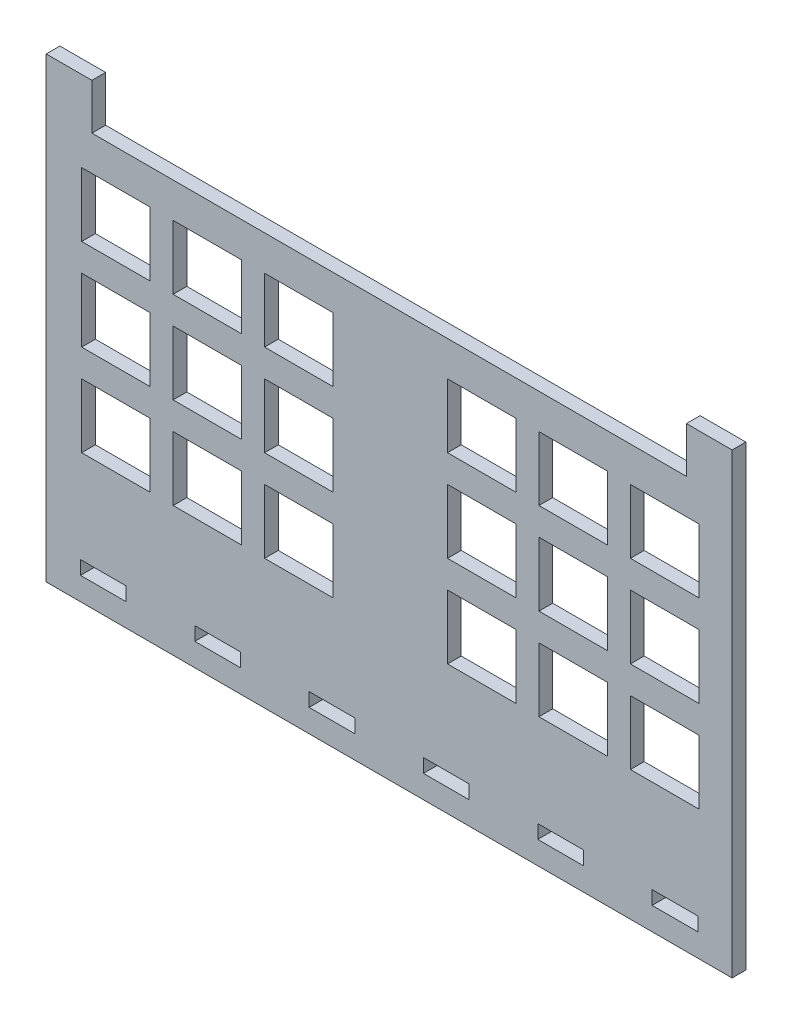
SolidWorks part; units mm, degrees
ref_plane "Plan de face" through (0, 0, 0) normal (0, 0, 1) x (1, 0, 0)
ref_plane "Plan de dessus" through (0, 0, 0) normal (0, 1, 0) x (1, 0, 0)
ref_plane "Plan de droite" through (0, 0, 0) normal (1, 0, 0) x (0, 0, -1)
sketch "Esquisse1" plane through (0, 0, 0) normal (0, 0, 1) x (1, 0, 0)
  line L1 (0, 0) -> (150, 0)
  line L2 (0, 0) -> (0, 100)
  line L3 (0, 100) -> (150, 100)
  line L4 (150, 0) -> (150, 100)
  dimension "D1" = 150
  dimension "D2" = 100
extrude "Boss.-Extru.1" add sketch "Esquisse1" along normal blind 3
sketch "Esquisse3" plane through (0, 0, 3) normal (0, 0, 1) x (1, 0, 0)
  line L0 (150, 100) -> (0, 100) construction
  line L1 (10, 100) -> (140, 100)
  line L2 (10, 100) -> (10, 90)
  line L3 (10, 90) -> (140, 90)
  line L4 (140, 100) -> (140, 90)
  line L5 (0, 100) -> (0, 0) construction
  line L6 (150, 0) -> (150, 100) construction
  dimension "D1" = 10
  dimension "D2" = 10
  dimension "D3" = 10
extrude "Enlèv. mat.-Extru.1" cut sketch "Esquisse3" against normal blind 3
sketch "Esquisse4" [suppressed] plane through (10, 0, 0) normal (1, 0, 0) x (0, 0, -1)
  line L0 (-1.5, 100) -> (-1.5, 90) construction
  line L1 (0, 100) -> (-3, 100) construction
  line L2 (0, 90) -> (-3, 90) construction
  circle A0 centre (-1.5, 98) radius 0.75
  dimension "D1" = 2
extrude "Enlèv. mat.-Extru.2" [suppressed] cut sketch "Esquisse4" against normal blind 200 and the other way blind 153
fillet "Congé1" [suppressed] radius 1
sketch "Esquisse8" plane through (150, 0, 0) normal (1, 0, 0) x (0, 0, -1)
  line L0 (0, 0) -> (0, 100) construction
  line L1 (-3, 0) -> (0, 0) construction
  line L2 (0, 3) -> (68.9365, -9.1554)
  line L3 (0, 33) -> (59.7575, 27.611)
  line L4 (59.7575, 27.611) -> (68.9365, -9.1554)
  line L5 (0, 33) -> (0, 3)
  point P0 (0, 3)
  point P5 (0, 33)
  dimension "D1" = 3
  dimension "D2" = 30
  dimension "D3" = 100
  dimension "D4" = 70
  dimension "D5" = 60
extrude "Boss.-Extru.5" [suppressed] add sketch "Esquisse8" against normal blind 3
sketch "Esquisse9" [suppressed] plane through (0, 0, 0) normal (-1, 0, 0) x (0, 0, 1)
  line L0 (0, 33) -> (-59.7575, 27.611)
  line L1 (-59.7575, 27.611) -> (-68.9365, -9.1554)
  line L2 (-68.9365, -9.1554) -> (0, 3)
  line L3 (0, 3) -> (0, 33)
extrude "Boss.-Extru.6" [suppressed] add sketch "Esquisse9" against normal blind 3
fillet "Congé4" [suppressed] radius 20
sketch "Esquisse10" plane through (0, 0, 3) normal (0, 0, 1) x (1, 0, 0)
  line L0 (10, 90) -> (140, 90) construction
  line L1 (45, 90) -> (105, 90)
  line L2 (45, 90) -> (45, 100)
  line L3 (45, 100) -> (105, 100)
  line L4 (105, 90) -> (105, 100)
  line L5 (10, 100) -> (0, 100) construction
  line L6 (150, 0) -> (150, 100) construction
  dimension "D1" = 60
  dimension "D2" = 45
extrude "Boss.-Extru.7" [suppressed] add sketch "Esquisse10" against normal blind 3
sketch "Esquisse12" plane through (0, 0, 3) normal (0, 0, 1) x (1, 0, 0)
  line L1 (7.5, 8) -> (17.5, 8)
  line L2 (7.5, 8) -> (7.5, 5)
  line L3 (7.5, 5) -> (17.5, 5)
  line L4 (17.5, 8) -> (17.5, 5)
  line L5 (32.5, 5) -> (42.5, 5)
  line L6 (32.5, 5) -> (32.5, 8)
  line L7 (32.5, 8) -> (42.5, 8)
  line L8 (42.5, 5) -> (42.5, 8)
  line L9 (57.5, 5) -> (67.5, 5)
  line L10 (57.5, 5) -> (57.5, 8)
  line L11 (57.5, 8) -> (67.5, 8)
  line L12 (67.5, 5) -> (67.5, 8)
  line L13 (82.5, 5) -> (92.5, 5)
  line L14 (82.5, 5) -> (82.5, 8)
  line L15 (82.5, 8) -> (92.5, 8)
  line L16 (92.5, 5) -> (92.5, 8)
  line L18 (107.5, 8) -> (117.5, 8)
  line L19 (107.5, 8) -> (107.5, 5)
  line L20 (107.5, 5) -> (117.5, 5)
  line L21 (117.5, 8) -> (117.5, 5)
  line L22 (132.5, 5) -> (142.5, 5)
  line L23 (132.5, 5) -> (132.5, 8)
  line L24 (132.5, 8) -> (142.5, 8)
  line L25 (142.5, 5) -> (142.5, 8)
extrude "Enlèv. mat.-Extru.3" cut sketch "Esquisse12" against normal blind 10
sketch "Esquisse13" plane through (0, 0, 3) normal (0, 0, 1) x (1, 0, 0)
  line L0 (27.7595, 68.3585) -> (42.7595, 68.3585)
  line L1 (7.7595, 82.3585) -> (22.7595, 82.3585)
  line L2 (7.7595, 82.3585) -> (7.7595, 68.3585)
  line L3 (7.7595, 68.3585) -> (22.7595, 68.3585)
  line L4 (22.7595, 82.3585) -> (22.7595, 68.3585)
  line L5 (27.7595, 82.3585) -> (27.7595, 68.3585)
  line L6 (27.7595, 82.3585) -> (42.7595, 82.3585)
  line L7 (42.7595, 82.3585) -> (42.7595, 68.3585)
  line L8 (47.7595, 68.3585) -> (62.7595, 68.3585)
  line L9 (47.7595, 82.3585) -> (47.7595, 68.3585)
  line L10 (47.7595, 82.3585) -> (62.7595, 82.3585)
  line L11 (62.7595, 82.3585) -> (62.7595, 68.3585)
  line L16 (87.7595, 68.3585) -> (102.7595, 68.3585)
  line L17 (87.7595, 82.3585) -> (87.7595, 68.3585)
  line L18 (87.7595, 82.3585) -> (102.7595, 82.3585)
  line L19 (102.7595, 82.3585) -> (102.7595, 68.3585)
  line L20 (107.7595, 68.3585) -> (122.7595, 68.3585)
  line L21 (107.7595, 82.3585) -> (107.7595, 68.3585)
  line L22 (107.7595, 82.3585) -> (122.7595, 82.3585)
  line L23 (122.7595, 82.3585) -> (122.7595, 68.3585)
  line L24 (127.7595, 68.3585) -> (142.7595, 68.3585)
  line L25 (127.7595, 82.3585) -> (127.7595, 68.3585)
  line L26 (127.7595, 82.3585) -> (142.7595, 82.3585)
  line L27 (142.7595, 82.3585) -> (142.7595, 68.3585)
  line L28 (7.7595, 62.3585) -> (22.7595, 62.3585)
  line L29 (7.7595, 62.3585) -> (7.7595, 48.3585)
  line L30 (7.7595, 48.3585) -> (22.7595, 48.3585)
  line L31 (22.7595, 62.3585) -> (22.7595, 48.3585)
  line L32 (27.7595, 48.3585) -> (42.7595, 48.3585)
  line L33 (27.7595, 62.3585) -> (27.7595, 48.3585)
  line L34 (27.7595, 62.3585) -> (42.7595, 62.3585)
  line L35 (42.7595, 62.3585) -> (42.7595, 48.3585)
  line L36 (47.7595, 62.3585) -> (47.7595, 48.3585)
  line L37 (47.7595, 48.3585) -> (62.7595, 48.3585)
  line L38 (62.7595, 62.3585) -> (62.7595, 48.3585)
  line L39 (47.7595, 62.3585) -> (62.7595, 62.3585)
  line L40 (102.7595, 62.3585) -> (102.7595, 48.3585)
  line L41 (87.7595, 48.3585) -> (102.7595, 48.3585)
  line L42 (87.7595, 62.3585) -> (87.7595, 48.3585)
  line L43 (87.7595, 62.3585) -> (102.7595, 62.3585)
  line L44 (107.7595, 62.3585) -> (122.7595, 62.3585)
  line L45 (107.7595, 62.3585) -> (107.7595, 48.3585)
  line L46 (107.7595, 48.3585) -> (122.7595, 48.3585)
  line L47 (122.7595, 62.3585) -> (122.7595, 48.3585)
  line L48 (127.7595, 62.3585) -> (127.7595, 48.3585)
  line L49 (127.7595, 48.3585) -> (142.7595, 48.3585)
  line L50 (142.7595, 62.3585) -> (142.7595, 48.3585)
  line L51 (127.7595, 62.3585) -> (142.7595, 62.3585)
  line L52 (7.7595, 42.3585) -> (22.7595, 42.3585)
  line L53 (7.7595, 42.3585) -> (7.7595, 28.3585)
  line L54 (7.7595, 28.3585) -> (22.7595, 28.3585)
  line L55 (22.7595, 42.3585) -> (22.7595, 28.3585)
  line L56 (27.7595, 28.3585) -> (42.7595, 28.3585)
  line L57 (27.7595, 42.3585) -> (27.7595, 28.3585)
  line L58 (27.7595, 42.3585) -> (42.7595, 42.3585)
  line L59 (42.7595, 42.3585) -> (42.7595, 28.3585)
  line L60 (47.7595, 42.3585) -> (47.7595, 28.3585)
  line L61 (47.7595, 28.3585) -> (62.7595, 28.3585)
  line L62 (62.7595, 42.3585) -> (62.7595, 28.3585)
  line L63 (47.7595, 42.3585) -> (62.7595, 42.3585)
  line L64 (102.7595, 42.3585) -> (102.7595, 28.3585)
  line L65 (87.7595, 28.3585) -> (102.7595, 28.3585)
  line L66 (87.7595, 42.3585) -> (87.7595, 28.3585)
  line L67 (87.7595, 42.3585) -> (102.7595, 42.3585)
  line L68 (107.7595, 42.3585) -> (122.7595, 42.3585)
  line L69 (107.7595, 42.3585) -> (107.7595, 28.3585)
  line L70 (107.7595, 28.3585) -> (122.7595, 28.3585)
  line L71 (122.7595, 42.3585) -> (122.7595, 28.3585)
  line L72 (127.7595, 42.3585) -> (127.7595, 28.3585)
  line L73 (127.7595, 28.3585) -> (142.7595, 28.3585)
  line L74 (142.7595, 42.3585) -> (142.7595, 28.3585)
  line L75 (127.7595, 42.3585) -> (142.7595, 42.3585)
  line L76 (67.7595, 68.3585) -> (82.7595, 68.3585) [skipped]
  line L77 (67.7595, 82.3585) -> (67.7595, 68.3585) [skipped]
  line L78 (67.7595, 82.3585) -> (82.7595, 82.3585) [skipped]
  line L79 (82.7595, 82.3585) -> (82.7595, 68.3585) [skipped]
  dimension "D1" = 15
  dimension "D2" = 14
  dimension "D3" = 7
  dimension "D4" = 3
extrude "Enlèv. mat.-Extru.4" cut sketch "Esquisse13" against normal blind 10
